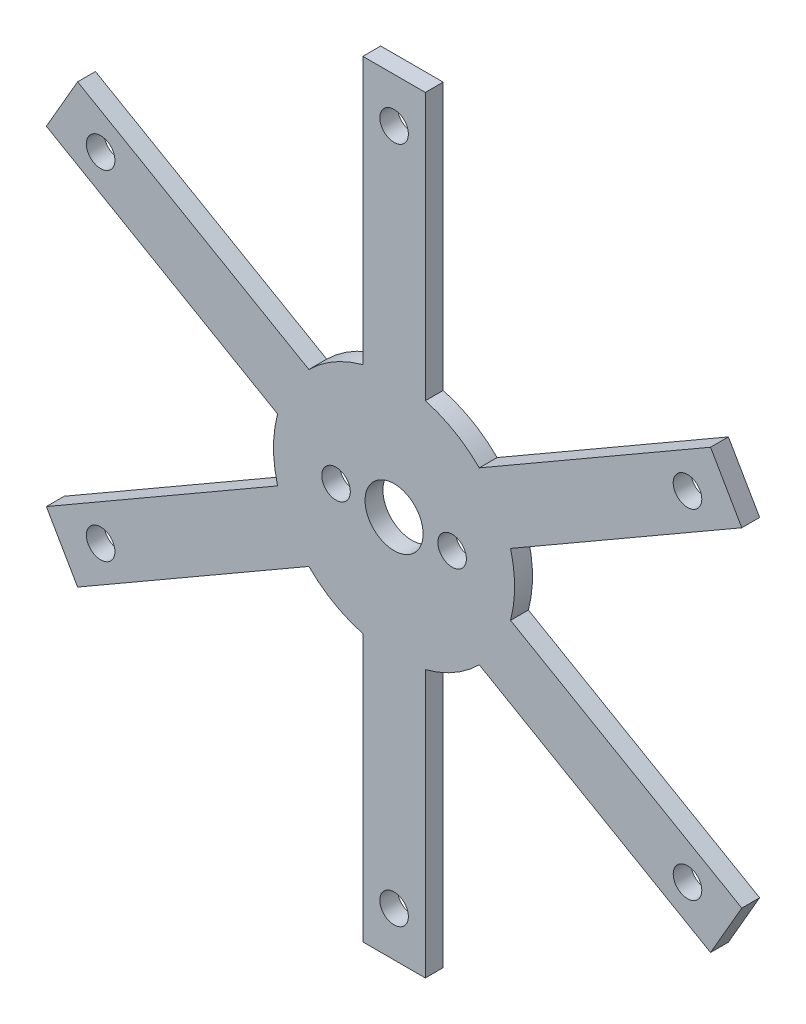
SolidWorks part; units mm, degrees
material "1060 合金"
ref_plane "正面" through (0, 0, 0) normal (0, 0, 1) x (1, 0, 0)
ref_plane "平面" through (0, 0, 0) normal (0, 1, 0) x (1, 0, 0)
ref_plane "右側面" through (0, 0, 0) normal (1, 0, 0) x (0, 0, -1)
sketch "ｽｹｯﾁ1" plane through (0, 0, 0) normal (0, 0, 1) x (1, 0, 0)
  line L0 (-6.5, 0) -> (6.5, 0)
  line L1 (0, 0) -> (37.1871, 21.47)
  line L6 (1.75, -3.0311) -> (-1.75, 3.0311)
  line L7 (35.4371, 24.5011) -> (38.9371, 18.4389)
  line L8 (38.9371, 18.4389) -> (1.75, -3.0311)
  line L9 (35.4371, 24.5011) -> (-1.75, 3.0311)
  circle A0 centre (0, 0) radius 13.5
  circle A1 centre (0, 0) radius 3.25
  circle A2 centre (6.5, 0) radius 1.6
  circle A3 centre (-6.5, 0) radius 1.6
  point P7 (0, 0)
  point P13 (0, 0)
  point P14 (0, 0)
  point P17 (37.1871, 21.47)
  dimension "D1" = 27
  dimension "D2" = 6.5
  dimension "D4" = 3.2
  dimension "D5" = 3.2
  dimension "D3" = 6.5
  dimension "D6" = 42.94
  dimension "D7" = 3.5
  dimension "D8" = 3.5
extrude "ﾎﾞｽ - 押し出し3" add sketch "ｽｹｯﾁ1" along normal blind 2 contours A3 A1 L6 L9 A0 L8 A2 | A1 L1 A0 L9 L6 | A2 L8 A0 L1 A1 L0 | A2 L0 A1 L6 L8 region at (8.4454, 3.104, 0) region at (3.7053, -1.1651, 0) region at (-1.8159, -3.1453, 0) region at (5.8614, 5.4831, 0)
extrude "ﾎﾞｽ - 押し出し4" add sketch "ｽｹｯﾁ1<7>" along normal blind 2 contours A0 L8 L7 L1 | A0 L1 L7 L9 region at (23.4955, 15.5911, 0) region at (25.2501, 12.5522, 0)
sketch "ｽｹｯﾁ1<7>" plane through (0, 0, 0) normal (0, 0, 1) x (1, 0, 0) same geometry as "ｽｹｯﾁ1"
pattern_circular "円形ﾊﾟﾀｰﾝ1" count 6 over 360 about axis through (0, 0, 2) along (0, 0, 1) of "ﾎﾞｽ - 押し出し4"
sketch "ｽｹｯﾁ2" plane through (0, 0, 2) normal (0, 0, 1) x (1, 0, 0)
  line L0 (0, 0) -> (32.857, 18.97)
  circle A0 centre (32.857, 18.97) radius 1.6
  dimension "D2" = 3.2
  dimension "D1" = 37.94
extrude "ｶｯﾄ - 押し出し1" cut sketch "ｽｹｯﾁ2" against normal up to next contours A0
pattern_circular "円形ﾊﾟﾀｰﾝ2" count 6 over 360 about axis through (0, 0, 2) along (0, 0, 1) of "ｶｯﾄ - 押し出し1"
